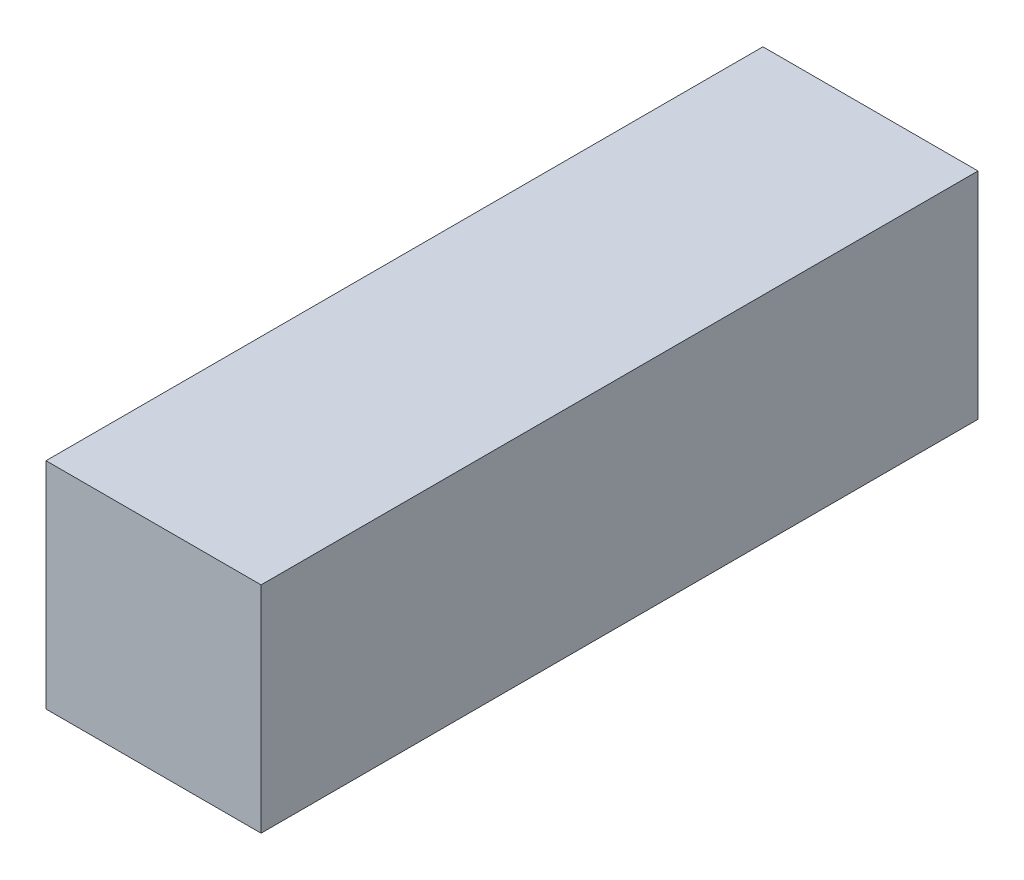
SolidWorks part; units mm, degrees
ref_plane "Front Plane" through (0, 0, 0) normal (0, 0, 1) x (1, 0, 0)
ref_plane "Top Plane" through (0, 0, 0) normal (0, 1, 0) x (1, 0, 0)
ref_plane "Right Plane" through (0, 0, 0) normal (1, 0, 0) x (0, 0, -1)
sketch "Sketch1" plane through (0, 0, 0) normal (0, 0, 1) x (1, 0, 0)
  line L3 (1.5, -1.5) -> (-1.5, -1.5)
  line L4 (1.5, -1.5) -> (1.5, 1.5)
  line L5 (1.5, 1.5) -> (-1.5, 1.5)
  line L6 (-1.5, -1.5) -> (-1.5, 1.5)
  line L7 (1.5, -1.5) -> (-1.5, 1.5) construction
  line L8 (1.5, 1.5) -> (-1.5, -1.5) construction
  point P0 (0, 0)
  dimension "Width" = 3
  dimension "Height" = 3
sketch "Sketch2" plane through (0, 0, 0) normal (1, 0, 0) x (0, 0, -1)
  line L0 (-3, 0) -> (3, 0) construction
  line L2 (5, -1.5) -> (-5, -1.5)
  line L3 (5, -1.5) -> (5, 1.5)
  line L4 (5, 1.5) -> (-5, 1.5)
  line L5 (-5, -1.5) -> (-5, 1.5)
  line L6 (5, -1.5) -> (-5, 1.5) construction
  line L7 (5, 1.5) -> (-5, -1.5) construction
  point P0 (0, 0)
  point P4 (0, 0)
  point P11 (3, 0)
  point P12 (-3, 0)
  point P14 (-2.01, 0)
  dimension "Length" = 10
  dimension "D1" = 6
  dimension "D3" = 0.99
sketch "Sketch3" plane through (0, 0, 0) normal (0, 0, 1) x (1, 0, 0)
  line L0 (1.5, -1.5) -> (1.5, 1.5) construction
  line L5 (1.5, -1.5) -> (-1.5, -1.5) construction
  line L6 (-1.5, -1.5) -> (-1.5, 1.5) construction
  line L7 (1.5, 1.5) -> (-1.5, 1.5) construction
  line L8 (1.5, -1.5) -> (1.5, 1.5)
  line L9 (1.5, -1.5) -> (-1.5, -1.5)
  line L10 (-1.5, -1.5) -> (-1.5, 1.5)
  line L11 (1.5, 1.5) -> (-1.5, 1.5)
extrude "Boss-Extrude1" add sketch "Sketch3" along normal up to vertex (5 mm away) and the other way up to vertex (5 mm away) up to point (0, 1.5, 5) other way up to point (0, 1.5, -5)
ref_plane "Contact Plane 1" through (0, 0, 5) normal (0, 0, 1) x (1, 0, 0)
ref_plane "Contact Plane 2" through (0, 0, -5) normal (0, 0, 1) x (1, 0, 0)
ref_axis "Center Axis 1" through (0, 0, -4.4) along (0, 0, 1)
equation "\"D1@Sketch2\"=\"Length@Sketch2\"*.6"
equation "\"D3@Sketch2\"=\"Width@Sketch1\"*.33"
